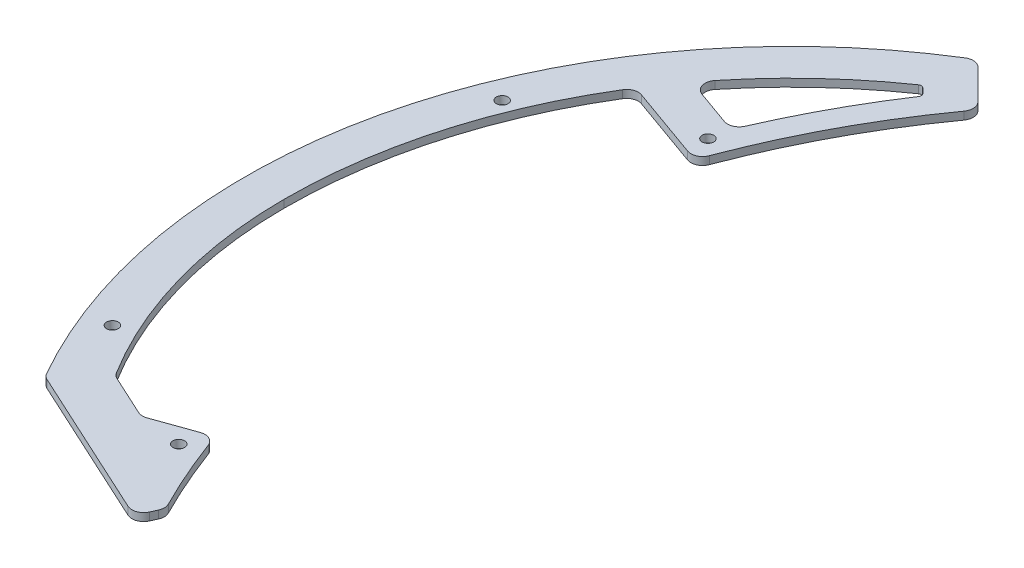
SolidWorks part; units mm, degrees
material "1060 Alloy"
ref_plane "Front Plane" through (0, 0, 0) normal (0, 0, 1) x (1, 0, 0)
ref_plane "Top Plane" through (0, 0, 0) normal (0, 1, 0) x (1, 0, 0)
ref_plane "Right Plane" through (0, 0, 0) normal (1, 0, 0) x (0, 0, -1)
sketch "Sketch1" plane through (0, 0, 0) normal (0, 1, 0) x (1, 0, 0)
  circle A0 centre (0, 0) radius 140
  dimension "D1" = 280
extrude "Boss-Extrude1" add sketch "Sketch1" along normal blind 2
sketch "Sketch19" plane through (0, 2, 0) normal (0, 1, 0) x (1, 0, 0)
  line L0 (-78.4889, 78.4889) -> (78.4889, -78.4889) construction
  line L1 (111, 45.9777) -> (45.9777, 111) construction
  line L2 (45.9777, 111) -> (-45.9777, 111) construction
  line L3 (-45.9777, 111) -> (-111, 45.9777) construction
  line L4 (-111, 45.9777) -> (-111, -45.9777) construction
  line L5 (-111, -45.9777) -> (-45.9777, -111) construction
  line L6 (-45.9777, -111) -> (45.9777, -111) construction
  line L7 (45.9777, -111) -> (111, -45.9777) construction
  line L8 (111, -45.9777) -> (111, 45.9777) construction
  line L9 (78.4889, 78.4889) -> (-78.4889, -78.4889) construction
  circle A0 centre (-89.0955, -67.8823) radius 1.5
  circle A1 centre (-89.0955, 67.8823) radius 1.5
  circle A2 centre (89.0955, 67.8823) radius 1.5
  circle A3 centre (89.0955, -67.8823) radius 1.5
  circle A4 centre (0, 0) radius 111 construction
  circle A5 centre (-67.8823, 89.0955) radius 1.5
  circle A6 centre (67.8823, 89.0955) radius 1.5
  circle A7 centre (67.8823, -89.0955) radius 1.5
  circle A8 centre (-67.8823, -89.0955) radius 1.5
  dimension "D5" = 3
  dimension "D1" = 15
  dimension "D6" = 111
extrude "Cut-Extrude3" cut sketch "Sketch19" against normal up to next
sketch "Sketch17" plane through (0, 0, 0) normal (0, -1, 0) x (1, 0, 0)
  line L0 (-50, 100) -> (-121.2436, 70)
  line L1 (-50, 100) -> (50, 100)
  line L2 (-121.2436, 70) -> (-121.2436, 140)
  line L3 (-121.2436, 140) -> (121.2436, 140)
  line L4 (121.2436, 140) -> (121.2436, 70)
  line L5 (121.2436, 70) -> (50, 100)
  circle A0 centre (0, 0) radius 140 construction
  dimension "D1" = 100
  dimension "D2" = 50
  dimension "D3" = 50
  dimension "D4" = 70
extrude "Cut-Extrude1" [suppressed] cut sketch "Sketch17" against normal up to next
sketch "Sketch25" plane through (0, 2, 0) normal (0, 1, 0) x (1, 0, 0)
  circle A0 centre (-124, 50) radius 1.5
  circle A1 centre (-124, -50) radius 1.5
  dimension "D1" = 3
  dimension "D2" = 50
  dimension "D3" = 50
  dimension "D4" = 124
extrude "Cut-Extrude10" cut sketch "Sketch25" against normal up to next
sketch "Sketch20" plane through (0, 2, 0) normal (0, 1, 0) x (1, 0, 0)
  line L0 (-72, 120.0666) -> (-50, 98.0666)
  line L1 (-50, 98.0666) -> (50, 98.0666)
  line L2 (50, 98.0666) -> (72, 120.0666)
  circle A1 centre (0, 0) radius 140 construction
  dimension "D1" = 144
  dimension "D2" = 100
  dimension "D3" = 50
extrude "Cut-Extrude4" cut sketch "Sketch20" against normal up to next
fillet "Fillet2" radius 10 2 edges at (50, 1, -98.0666) (-50, 1, -98.0666)
sketch "Sketch26" plane through (0, 2, 0) normal (0, 1, 0) x (1, 0, 0)
  line L0 (-121.2436, -70) -> (-79.057, -89.4493)
  line L1 (-79.057, -89.4493) -> (-76.4598, -83.816)
  line L2 (-100.1421, -66.5145) -> (-86.1288, -61.5152)
  line L3 (-86.1288, -61.5152) -> (-93.657, -40.4132) construction
  line L4 (-109.6127, 69.8932) -> (-86.1288, 61.5152)
  line L5 (-60.85, 108.9167) -> (-72, 120.0666)
  line L6 (-72, 120.0666) -> (-52.9289, 100.9956) construction
  line L7 (-86.1288, 61.5152) -> (-98.4946, 26.8531) construction
  line L8 (-112.4256, -60.8515) -> (-100.1421, -66.5145)
  line L9 (-130, 74.1477) -> (-130, -50) construction
  line L10 (-103.6984, 78.4005) -> (-88.1706, 72.861)
  line L11 (-73.3831, 107.3076) -> (-70.9931, 104.9176)
  circle A0 centre (-67.8823, 89.0955) radius 5 construction
  circle A1 centre (-89.0955, 67.8823) radius 5 construction
  circle A2 centre (-124, 50) radius 5 construction
  circle A3 centre (-89.0955, -67.8823) radius 5 construction
  circle A4 centre (-67.8823, -89.0955) radius 5 construction
  circle A5 centre (-124, -50) radius 5 construction
  arc A6 (-112.4256, -60.8515) -> (-130, 0) centre (-15.8636, 0) cw
  arc A7 (-72, 120.0666) -> (72, 120.0666) centre (0, 0) ccw construction
  arc A8 (-86.1288, -61.5152) -> (-76.4598, -83.816) centre (86.3028, 0) ccw
  arc A9 (-86.1288, 61.5152) -> (-60.85, 108.9167) centre (86.3028, 0) cw
  arc A10 (-130, 0) -> (-109.6127, 69.8932) centre (0, 0) cw
  arc A11 (-73.3831, 107.3076) -> (-103.6984, 78.4005) centre (0, 0) ccw
  arc A12 (-88.1706, 72.861) -> (-70.9931, 104.9176) centre (86.3028, 0) cw
  arc A13 (-72, 120.0666) -> (-121.2436, -70) centre (0, 0) ccw
  circle M1 centre (-89.0955, -67.8823) radius 1.5
  circle M2 centre (-89.0955, 67.8823) radius 1.5
  circle M3 centre (89.0955, 67.8823) radius 1.5
  circle M4 centre (89.0955, -67.8823) radius 1.5
  circle M5 centre (-67.8823, 89.0955) radius 1.5
  circle M6 centre (67.8823, 89.0955) radius 1.5
  circle M7 centre (67.8823, -89.0955) radius 1.5
  circle M8 centre (-67.8823, -89.0955) radius 1.5
  circle M9 centre (-124, 50) radius 1.5
  circle M10 centre (-124, -50) radius 1.5
  arc M11 (-72, 120.0666) -> (72, 120.0666) centre (0, 0) ccw
  line M12 (72, 120.0666) -> (52.9289, 100.9956)
  arc M13 (52.9289, 100.9956) -> (45.8579, 98.0666) centre (45.8579, 108.0666) cw
  line M14 (45.8579, 98.0666) -> (-45.8579, 98.0666)
  arc M15 (-45.8579, 98.0666) -> (-52.9289, 100.9956) centre (-45.8579, 108.0666) cw
  line M16 (-52.9289, 100.9956) -> (-72, 120.0666)
  dimension "D1" = 10
  dimension "D4" = 12
  dimension "D5" = 130
  dimension "D6" = 6
  dimension "D7" = 10
  dimension "D2" = 70
  dimension "D3" = 10
  dimension "D8" = 10
  dimension "D9" = 10
extrude "Cut-Extrude11" cut sketch "Sketch26" against normal up to next (2 mm away) contours A10 A6 L8 L2 A8 L1 L0 A9 L4 M11 M12 M13 M14 M15 M16 M4 M6 M8 M7 M5 M3 | L10 A12 L11 A11 | M5 | M2 | M9 | M1 | M10 region at (7.3149, 2, 12.0107) region at (-87.3194, 2, -88.2203) region at (-89.0955, 2, 67.8823) region at (-89.0955, 2, -67.8823) region at (-67.8823, 2, -89.0955) region at (-124, 2, -50) region at (-124, 2, 50)
sketch "Sketch23" [suppressed] plane through (0, 3, 0) normal (0, 1, 0) x (1, 0, 0)
  line L0 (-72.365, -73.9737) -> (-80.4987, -93.2894)
  line L1 (-72, 120.0666) -> (-52.9289, 100.9956) construction
  line L2 (-121.2436, -70) -> (-50, -100) construction
  arc A0 (-54.9334, 103) -> (-72.365, -73.9737) centre (114.6363, -3.0477) ccw
  arc A3 (-72.365, -73.9737) -> (-54.9334, -109.0955) centre (114.6363, -3.0477) ccw construction
  circle A4 centre (-67.8823, -89.0955) radius 1.5 construction
  dimension "D1" = 103
  dimension "D2" = 20
  dimension "D3" = 200
  dimension "D4" = 90
  dimension "D5" = 10
extrude "Cut-Extrude8" [suppressed] cut sketch "Sketch23" against normal through all and the other way through all
sketch "Sketch24" [suppressed] plane through (0, 3, 0) normal (0, 1, 0) x (1, 0, 0)
  line L0 (-87.2371, 61.6912) -> (-76.1181, 57.0584)
  line L1 (-108.2916, -62.4334) -> (-85.8817, -71.87)
  line L3 (-121.2436, -70) -> (-78.3054, -88.0808) construction
  line L4 (-88.8916, -62.3806) -> (-77.7417, -57.7349)
  line L5 (-120, 50) -> (0, 0) construction
  line L6 (0, 0) -> (-120, -50) construction
  line L7 (-76.1181, 57.0584) -> (-77.7417, -57.7349)
  arc A1 (-87.2371, 61.6912) -> (-67.7264, 105.0625) centre (114.6363, -3.0477) cw
  arc A2 (-54.9334, 103) -> (-72.365, -73.9737) centre (114.6363, -3.0477) ccw construction
  arc A3 (-67.7264, 105.0625) -> (-108.2916, -62.4334) centre (0, 0) ccw
  circle A4 centre (-120, 50) radius 5 construction
  circle A5 centre (-120, -50) radius 5 construction
  arc A6 (-85.8817, -71.87) -> (-88.8916, -62.3806) centre (114.6363, -3.0477) cw
  circle A8 centre (-89.0955, -67.8823) radius 1.5 construction
  circle A9 centre (-89.0955, 67.8823) radius 1.5 construction
  dimension "D2" = 10
  dimension "D3" = 5
  dimension "D4" = 12
  dimension "D5" = 12
  dimension "D1" = 5
  dimension "D6" = 12
extrude "Cut-Extrude9" [suppressed] cut sketch "Sketch24" against normal up to next
fillet "Fillet4" [suppressed] radius 5
fillet "Fillet5" [suppressed] radius 3
fillet "Fillet6" radius 3 12 edges at (-72, 1, -120.0666) (-88.1706, 1, -72.861) (-103.6984, 1, -78.4005) (-112.4256, 1, 60.8515) (-100.1421, 1, 66.5145) (-86.1288, 1, 61.5152) (-76.4598, 1, 83.816) (-79.057, 1, 89.4493) (-109.6127, 1, -69.8932) (-86.1288, 1, -61.5152) (-60.85, 1, -108.9167) (-121.2436, 1, 70)
fillet "Fillet7" radius 1 2 edges at (-73.3831, 1, -107.3076) (-70.9931, 1, -104.9176)
equation "\"D3@Sketch20\" = \"D2@Sketch20\" / 2"
